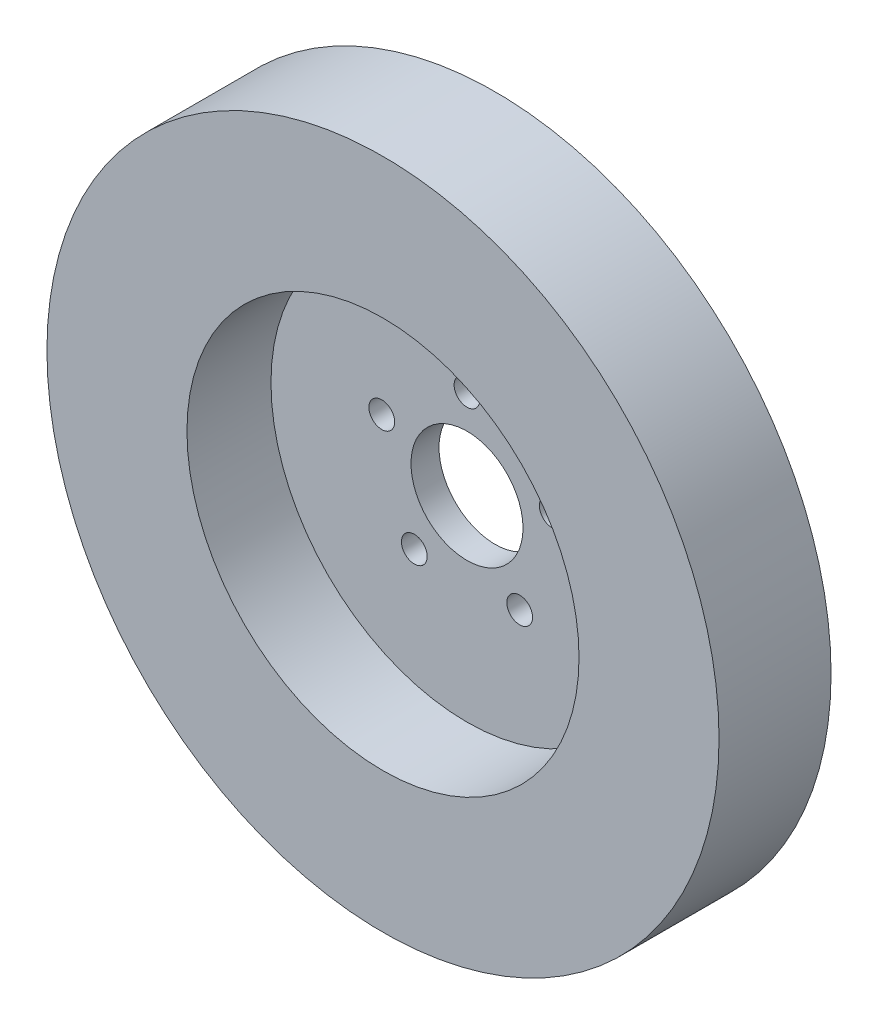
SolidWorks part; units mm, degrees
ref_plane "Front Plane" through (0, 0, 0) normal (0, 0, 1) x (1, 0, 0)
ref_plane "Top Plane" through (0, 0, 0) normal (0, 1, 0) x (1, 0, 0)
ref_plane "Right Plane" through (0, 0, 0) normal (1, 0, 0) x (0, 0, -1)
sketch "Sketch1" plane through (0, 0, 0) normal (0, 0, 1) x (1, 0, 0)
  line L0 (0, 0) -> (0, 20.32) construction
  line L1 (0, 0) -> (19.3255, 6.2792) construction
  line L2 (0, 0) -> (11.9438, -16.4392) construction
  line L3 (0, 0) -> (-11.9438, -16.4392) construction
  line L4 (0, 0) -> (-19.3255, 6.2792) construction
  circle A0 centre (0, 0) radius 76.2
  circle A1 centre (0, 0) radius 12.7
  circle A2 centre (0, 20.32) radius 2.921
  circle A3 centre (19.3255, 6.2792) radius 2.921
  circle A4 centre (11.9438, -16.4392) radius 2.921
  circle A5 centre (-11.9438, -16.4392) radius 2.921
  circle A6 centre (-19.3255, 6.2792) radius 2.921
  point P17 (0, 0)
  dimension "D1" = 25.4
  dimension "D2" = 152.4
  dimension "D3" = 5.842
  dimension "D5" = 20.32
  dimension "D4" = 5
extrude "Boss-Extrude2" add sketch "Sketch1" along normal blind 25.4
sketch "Sketch2" plane through (0, 0, 25.4) normal (0, 0, 1) x (1, 0, 0)
  circle A0 centre (0, 0) radius 44.45
  dimension "D1" = 88.9
extrude "Cut-Extrude1" cut sketch "Sketch2" against normal blind 19.05
